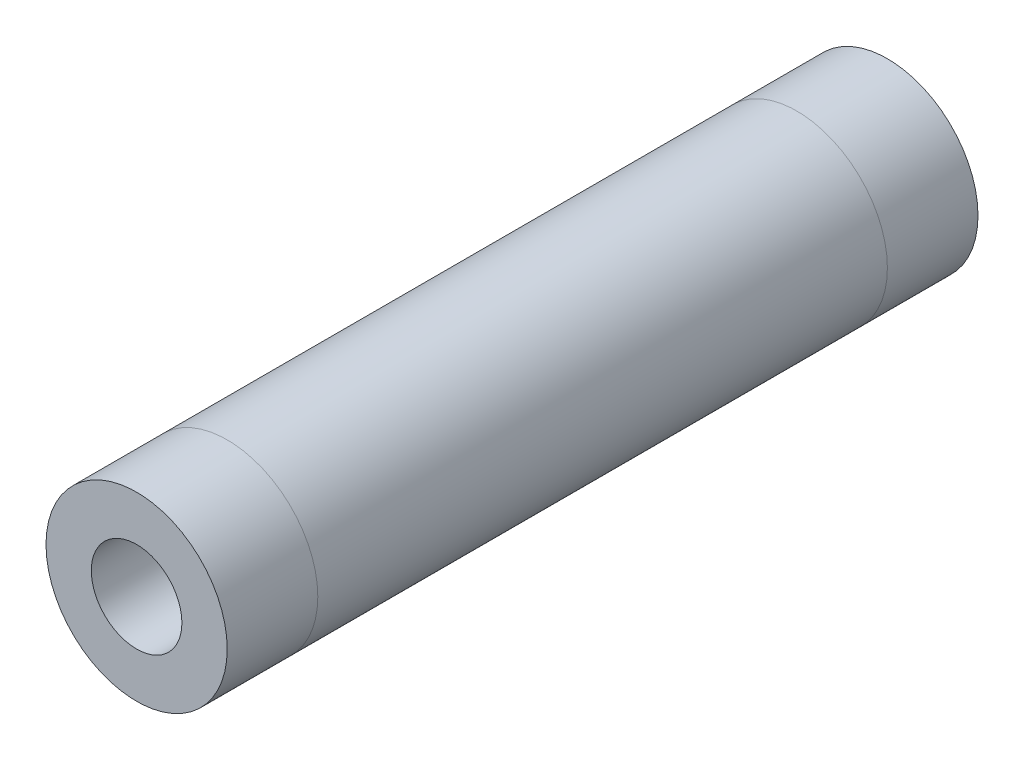
SolidWorks part; units mm, degrees
material "AISI 4130 Steel, normalized at 870C"
ref_plane "Front Plane" through (0, 0, 0) normal (0, 0, 1) x (1, 0, 0)
ref_plane "Top Plane" through (0, 0, 0) normal (0, 1, 0) x (1, 0, 0)
ref_plane "Right Plane" through (0, 0, 0) normal (1, 0, 0) x (0, 0, -1)
sketch "Axis" plane through (0, 0, 0) normal (0, 1, 0) x (1, 0, 0)
  line L0 (0, 0) -> (0, 21.9075) construction
  line L1 (0, 21.9075) -> (0, 74.5274) construction
  line L2 (0, 74.5274) -> (0, 96.4349) construction
  dimension "D1" = 21.9075
  dimension "D2" = 96.4349
sketch "Sketch2" plane through (0, 0, 0) normal (0, 0, 1) x (1, 0, 0)
  circle A0 centre (0, 0) radius 6.35
  circle A1 centre (0, 0) radius 3.175
  circle A2 centre (0, 0) radius 4.7625
  dimension "D1" = 12.7
  dimension "D2" = 6.35
  dimension "D3" = 9.525
extrude "Threaded Insert 1-1" add sketch "Sketch2" against normal blind 6.35 from vertex contours A0 A2 | A2 A1 region at (-6.1704, 0, 0) region at (-4.6278, 0, 0) starting at point (0, 0, -21.9075)
extrude "Threaded Insert 1-2" add sketch "Sketch2<5>" against normal blind 6.35 from surface contours A2 A1 region at (-4.6278, 0, 0) starting at face at (6.35, 0, -28.2575)
sketch "Sketch2<5>" plane through (0, 0, 0) normal (0, 0, 1) x (1, 0, 0) same geometry as "Sketch2"
extrude "Boss-Extrude4" add sketch "Sketch2<7>" along normal blind 6.35 from vertex separate body contours A0 A2 | A2 A1 region at (-6.1704, 0, 0) region at (-4.6278, 0, 0) starting at point (0, 0, -74.5274)
sketch "Sketch2<7>" plane through (0, 0, 0) normal (0, 0, 1) x (1, 0, 0) same geometry as "Sketch2"
extrude "Boss-Extrude5" add sketch "Sketch2<8>" along normal blind 6.35 from surface contours A2 A1 region at (-4.6278, 0, 0) starting at face at (6.35, 0, -68.1774)
sketch "Sketch2<8>" plane through (0, 0, 0) normal (0, 0, 1) x (1, 0, 0) same geometry as "Sketch2"
extrude "Boss-Extrude6" add sketch "Sketch2<9>" against normal up to surface (68.1774 mm away) from surface separate body contours A0 A2 region at (-6.1704, 0, 0) up to face at (6.35, 0, -68.1774) starting at face at (4.7625, 0, -28.2575)
sketch "Sketch2<9>" plane through (0, 0, 0) normal (0, 0, 1) x (1, 0, 0) same geometry as "Sketch2"
equation "\"Tube Outer Diameter\"= .5"
equation "\"Tube Inner Diameter\"= .375"
equation "\"Rod end Diameter\"= .25"
equation "\"Threaded Insert Out\"= .25"
equation "\"Threaded Insert In\"= .25'`"
equation "\"D1@Sketch2\"=\"Tube Outer Diameter\""
equation "\"D2@Sketch2\"=\"Rod end Diameter\""
equation "\"D1@Threaded Insert 1-1\" = \"Threaded Insert Out\""
equation "\"D3@Sketch2\"=\"Tube Inner Diameter\""
equation "\"D1@Threaded Insert 1-2\" = \"Threaded Insert In\""
equation "\"D1@Boss-Extrude4\"=\"Threaded Insert Out\""
equation "\"D1@Boss-Extrude5\"=\"Threaded Insert In\""
